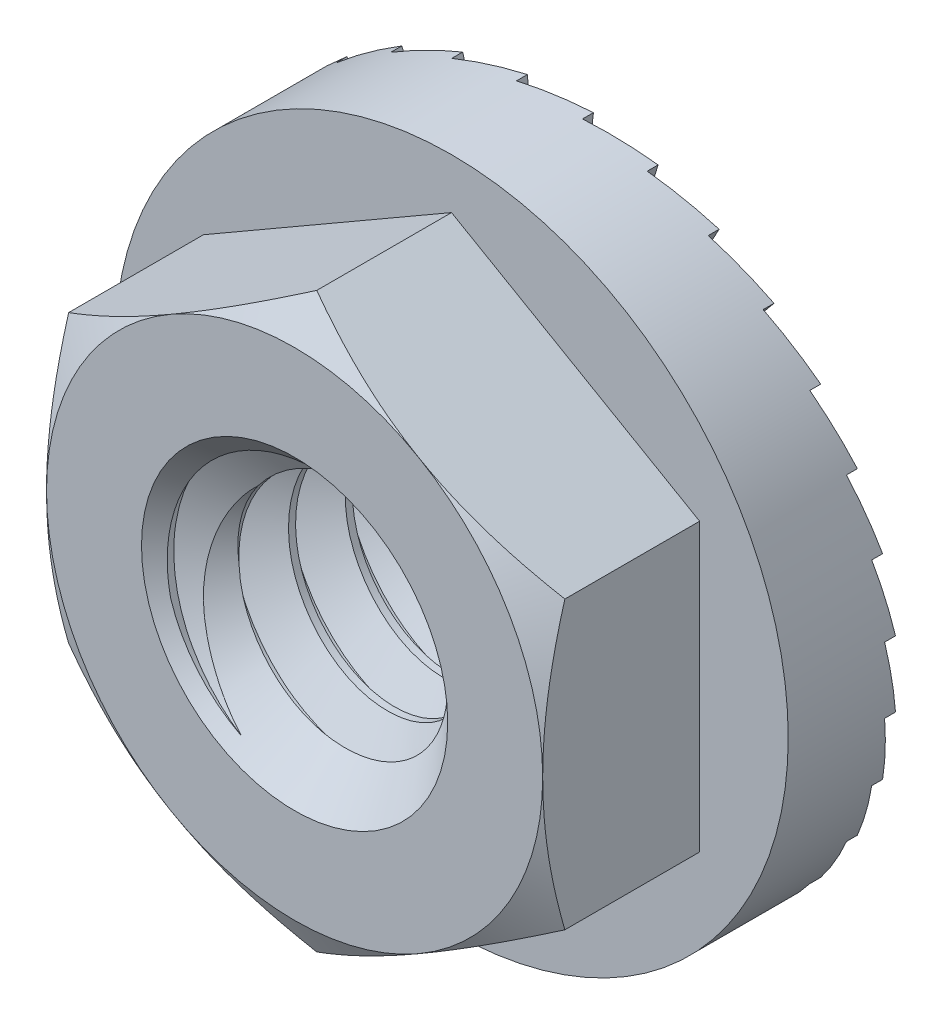
SolidWorks part; units mm, degrees
material "AISI 316 Stainless Steel Sheet (SS)"
ref_plane "Front Plane" through (0, 0, 0) normal (0, 0, 1) x (1, 0, 0)
ref_plane "Top Plane" through (0, 0, 0) normal (0, 1, 0) x (1, 0, 0)
ref_plane "Right Plane" through (0, 0, 0) normal (1, 0, 0) x (0, 0, -1)
sketch "Sketch1" plane through (0, 0, 0) normal (0, 0, 1) x (1, 0, 0)
  line L1 (0, 6.4158) -> (-5.5563, 3.2079)
  line L2 (-5.5563, 3.2079) -> (-5.5563, -3.2079)
  line L3 (-5.5563, -3.2079) -> (0, -6.4158)
  line L4 (0, -6.4158) -> (5.5562, -3.2079)
  line L5 (5.5562, -3.2079) -> (5.5562, 3.2079)
  line L6 (5.5562, 3.2079) -> (0, 6.4158)
  circle A0 centre (0, 0) radius 5.5563 construction
  dimension "Hex" = 11.1125
extrude "Extrude1" add sketch "Sketch1" against normal blind 5.9531
sketch "Sketch13" plane through (0, 0, -5.9531) normal (0, 0, -1) x (-1, 0, 0)
  circle A0 centre (0, 0) radius 7.5406
  dimension "Flange od" = 15.0812
extrude "Extrude3" add sketch "Sketch13" against normal blind 2.4384
sketch "Sketch2" plane through (0, 0, 0) normal (0, 0, 1) x (1, 0, 0)
  circle A0 centre (0, 0) radius 5.5563 construction
  circle A1 centre (0, 0) radius 5.5563
extrude "Cut-Extrude1" cut sketch "Sketch2" against normal through all draft 60 flip side to cut
sketch "Sketch4" plane through (0, 0, 0) normal (0, 0, 1) x (1, 0, 0)
  circle A0 centre (0, 0) radius 3.175
  dimension "Thread Dia" = 6.35
extrude "Cut-Extrude3" cut sketch "Sketch4" against normal through all
sketch "Sketch7" plane through (0, 0, 0) normal (0, 0, 1) x (1, 0, 0)
  circle A4 centre (0, 0) radius 3.429
  circle A5 centre (0, 0) radius 3.429
  dimension "D1" = 0.254
sketch "Sketch8" plane through (0, 0, -5.9531) normal (0, 0, -1) x (-1, 0, 0)
  circle A1 centre (0, 0) radius 3.429
  circle A2 centre (0, 0) radius 3.429 construction
sketch "Sketch5" plane through (0, 0, 0) normal (0, 0, 1) x (1, 0, 0)
  circle A0 centre (0, 0) radius 3.175 construction
  circle A1 centre (0, 0) radius 3.175
curve "Helix/Spiral1" pitch 1.27 height 7.2231 radius 3.175 centre (0, 0, 0) axis (0, 0, -1) start towards (0, 1, 0) parameters "pitch"=1.27
sketch "Sketch9" plane through (0, 0, 0) normal (1, 0, 0) x (0, 0, -1)
  line L0 (-0.635, 3.175) -> (-0.4762, 3.175)
  line L1 (-0.4762, 3.175) -> (0, 2.3501)
  line L2 (-0.635, 3.175) -> (-1.1112, 2.3501)
  line L3 (-1.1112, 2.3501) -> (0, 2.3501)
  line L4 (-0.5556, 3.175) -> (-0.5556, 2.3501) construction
  line L5 (-0.8731, 2.7626) -> (-0.2381, 2.7626) construction
  line L7 (0, 2.3501) -> (0, 3.175) construction
  line L8 (0, 3.175) -> (0, -3.175) construction
  dimension "D1" = 0.1588
  dimension "D2" = 0.635
  dimension "D3" = 60
sketch "Sketch12" plane through (0, 0, 0) normal (0, 0, 1) x (1, 0, 0)
  circle A0 centre (0, 0) radius 2.3501
  circle A1 centre (0, 0) radius 3.175 construction
  circle A2 centre (0, 0) radius 3.175
extrude "Extrude2" add sketch "Sketch12" against normal up to surface (5.9531 mm away) up to face at (3.175, 0, -5.9531)
sweep "Cut-Sweep1" cut profiles "Sketch9" path "Helix/Spiral1" align with end faces yes
extrude "Cut-Extrude6" cut sketch "Sketch7" against normal through all draft 45
extrude "Cut-Extrude7" cut sketch "Sketch8" against normal through all draft 45
sketch "Sketch14" plane through (0, 0, -5.9531) normal (0, 0, -1) x (-1, 0, 0)
  circle A4 centre (0, 0) radius 5.461
  circle A5 centre (0, 0) radius 5.461
  dimension "D1" = 2.032
extrude "Cut-Extrude8" cut sketch "Sketch14" against normal blind 0.2438 flip side to cut
sketch "Sketch15" plane through (0, 0, -5.7093) normal (0, 0, -1) x (-1, 0, 0)
  line L0 (-0.5353, 5.4347) -> (-0.7391, 7.5043)
  line L1 (0.5353, 5.4347) -> (0.7391, 7.5043)
  line L2 (0, 0) -> (0.5353, 5.4347) construction
  line L3 (0, 0) -> (-0.5353, 5.4347) construction
  circle A0 centre (0, 0) radius 7.5406 construction
  circle A1 centre (0, 0) radius 5.461 construction
  arc A2 (0.7391, 7.5043) -> (-0.7391, 7.5043) centre (0, 0) ccw
  arc A3 (0.5353, 5.4347) -> (-0.5353, 5.4347) centre (0, 0) ccw
  dimension "D1" = 11.25
extrude "Extrude4" add sketch "Sketch15" along normal up to surface (0.2438 mm away) separate body up to face at (-3.429, 0, -5.9531)
sketch "Sketch16" plane through (0, 0, 0) normal (0, 1, 0) x (1, 0, 0)
  line L0 (-0.7391, 5.7093) -> (0.7391, 5.9531)
  line L4 (-0.7391, 5.7093) -> (0.7391, 5.7093)
  line L5 (0.7391, 5.7093) -> (0.7391, 5.9531)
  line L6 (0.7391, 5.9531) -> (-0.7391, 5.9531)
  line L7 (-0.7391, 5.9531) -> (-0.7391, 5.7093)
  line L8 (-0.7391, 5.7093) -> (0.7391, 5.7093) construction
  line L9 (0.7391, 5.7093) -> (0.7391, 5.9531) construction
  line L10 (0.7391, 5.9531) -> (-0.7391, 5.9531)
  line L11 (-0.7391, 5.9531) -> (-0.7391, 5.7093)
  dimension "D1" = 0
extrude "Cut-Extrude9" cut sketch "Sketch16" along normal through all
pattern_circular "CirPattern1" count 32 over 360 about axis through (0, 0, -8.5261) along (0, 0, 1) of bodies 119
combine bodies "Combine1" operation type add bodies to combine 117 119 120 121 122 123 124 125 126 127 128 129 130 131 132 133 134 135 136 137 139 140 141 142 143 144 145 146 147 148 149 150 151
sketch "Sketch17" plane through (0, 0, 0) normal (1, 0, 0) x (0, 0, -1)
  line L0 (5.9531, 7.5406) -> (5.9531, -7.5406) construction
  line L1 (3.5147, 7.5406) -> (3.5147, -7.5406) construction
  dimension "D1" = 2.4384
sketch "Sketch18" plane through (0, 0, -3.5147) normal (0, 0, 1) x (1, 0, 0)
  circle A0 centre (0, 0) radius 7.5406
  circle A1 centre (0, 0) radius 7.5406 construction
equation "\"D2@Sketch9\" = \"pitch@Helix/Spiral1\"*.5"
equation "\"D3@Helix/Spiral1\" = \"pitch@Helix/Spiral1\"+\"Height@Extrude1\""
equation "\"D1@Sketch9\" = \"pitch@Helix/Spiral1\"*.125"
equation "\"D1@Cut-Extrude8\" = \"flange thickness@Extrude3\"*.1"
equation "\"D1@Sketch17\" = \"flange thickness@Extrude3\""
